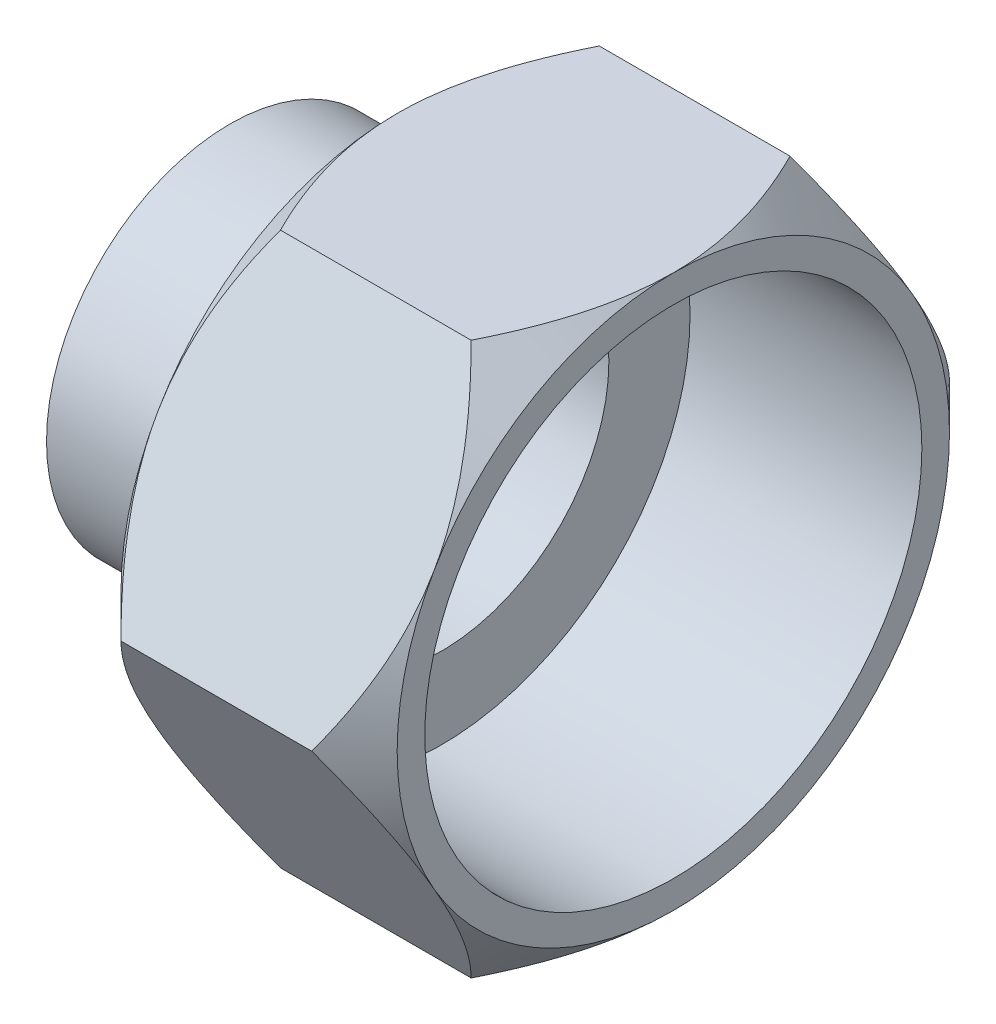
SolidWorks part; units mm, degrees
material "PE Высокой плотности"
ref_plane "Front" through (0, 0, 0) normal (0, 0, 1) x (1, 0, 0)
ref_plane "Top" through (0, 0, 0) normal (0, 1, 0) x (1, 0, 0)
ref_plane "Right" through (0, 0, 0) normal (1, 0, 0) x (0, 0, -1)
sketch "Эскиз1" plane through (0, 0, 0) normal (1, 0, 0) x (0, 0, -1)
  circle A0 centre (0, 0) radius 20
  dimension "d" = 40
extrude "Вытянуть-Тонкостенный1" add sketch "Эскиз1" along normal blind 20 thin thin type one direction wall 1.9
sketch "Эскиз2" plane through (20, 0, 0) normal (1, 0, 0) x (0, 0, -1)
  line L0 (50, 0) -> (-50, 0) construction
  line L1 (38.1051, 0) -> (19.0526, 33)
  line L2 (19.0526, 33) -> (-19.0526, 33)
  line L3 (-19.0526, 33) -> (-38.1051, 0)
  line L4 (-38.1051, 0) -> (-19.0526, -33)
  line L5 (-19.0526, -33) -> (19.0526, -33)
  line L6 (19.0526, -33) -> (38.1051, 0)
  circle A1 centre (0, 0) radius 33 construction
  dimension "D2" = 66
extrude "Бобышка-Вытянуть2" add sketch "Эскиз2" along normal blind 33
sketch "Эскиз8" plane through (20, 0, 0) normal (-1, 0, 0) x (0, 0, 1)
  circle A0 centre (0, 0) radius 33 construction
  circle A1 centre (0, 0) radius 33
extrude "Вырез-Вытянуть4" cut sketch "Эскиз8" against normal blind 10 draft 45 flip side to cut
sketch "Эскиз9" plane through (53, 0, 0) normal (1, 0, 0) x (0, 0, -1)
  circle A0 centre (0, 0) radius 33 construction
  circle A1 centre (0, 0) radius 33
extrude "Вырез-Вытянуть5" cut sketch "Эскиз9" against normal blind 10 draft 45 flip side to cut
sketch "Эскиз10" plane through (53, 0, 0) normal (1, 0, 0) x (0, 0, -1)
  circle A0 centre (0, 0) radius 29.7
  dimension "R1" = 59.4
sketch3d "Трехмерный эскиз1"
  line L0 (0, 0, 0) -> (53, 0, 0) construction
other "Точка соединения1" parameters "Диаметр"=40, "StubLength"=0
ref_axis "Ось1" through (-10, 0, 0) along (1, 0, 0)
extrude "Вырез-Вытянуть6" cut sketch "Эскиз10" against normal blind 27.7
sketch "Эскиз11" plane through (25.3, 0, 0) normal (1, 0, 0) x (0, 0, -1)
  circle A0 centre (0, 0) radius 20 construction
  circle A1 centre (0, 0) radius 20
extrude "Вырез-Вытянуть7" cut sketch "Эскиз11" against normal through all
